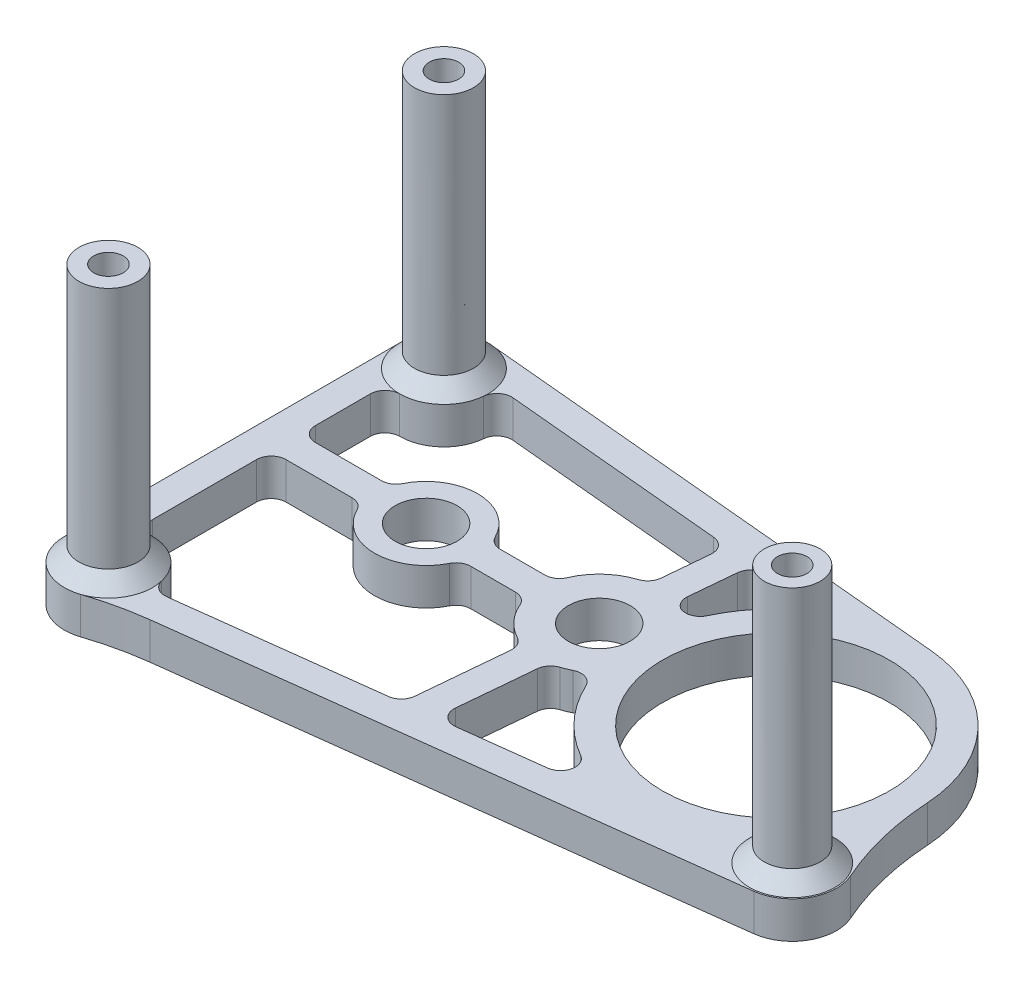
SolidWorks part; units mm, degrees
material "ABS"
ref_plane "Front Plane" through (0, 0, 0) normal (0, 0, 1) x (1, 0, 0)
ref_plane "Top Plane" through (0, 0, 0) normal (0, 1, 0) x (1, 0, 0)
ref_plane "Right Plane" through (0, 0, 0) normal (1, 0, 0) x (0, 0, -1)
sketch "Sketch2" plane through (0, 0, 0) normal (0, 1, 0) x (1, 0, 0)
  line L0 (-4.4632, 0) -> (-19.7032, 0)
  line L1 (-65.8645, -28.6002) -> (31.8874, -28.6002)
  line L2 (-65.8645, -28.6002) -> (-65.8645, 29.6837)
  line L3 (-65.8645, 29.6837) -> (31.8874, 29.6837)
  line L4 (31.8874, -28.6002) -> (31.8874, 29.6837)
  circle A0 centre (-4.4632, 0) radius 3.175 construction
  circle A1 centre (-19.7032, 0) radius 12.065 construction
  circle A2 centre (-4.4632, 0) radius 9.779
  circle A3 centre (-19.7032, 0) radius 2.667
  point P0 (0, 0)
  dimension "D1" = 6.35
  dimension "D2" = 24.13
  dimension "D3" = 19.558
  dimension "D5" = 5.334
  dimension "D4" = 15.24
extrude "Boss-Extrude1" add sketch "Sketch2" along normal blind 3.175
sketch "Sketch3" plane through (0, 3.175, 0) normal (0, 1, 0) x (1, 0, 0)
  line L4 (-65.8645, -28.6002) -> (31.8874, -28.6002)
  line L5 (31.8874, -28.6002) -> (31.8874, 29.6837)
  line L6 (31.8874, 29.6837) -> (-65.8645, 29.6837)
  line L7 (-65.8645, 29.6837) -> (-65.8645, -28.6002)
  line L8 (-65.8645, -28.6002) -> (31.8874, -28.6002)
  line L9 (31.8874, -28.6002) -> (31.8874, 29.6837)
  line L10 (31.8874, 29.6837) -> (-65.8645, 29.6837)
  line L11 (-65.8645, 29.6837) -> (-65.8645, -28.6002)
  dimension "D1" = 0
sketch "Sketch4" plane through (0, 3.175, 0) normal (0, 1, 0) x (1, 0, 0)
  line L0 (31.8874, -28.6002) -> (31.8874, 29.6837) construction
  line L1 (-65.8645, -28.6002) -> (31.8874, -28.6002) construction
  circle A0 centre (6.4874, -9.5502) radius 2.413
  circle A1 centre (6.4874, -9.5502) radius 1.27
  circle A2 centre (-45.4353, 12.3467) radius 1.27 construction
  circle A3 centre (-45.4353, 12.3467) radius 1.27
  circle A4 centre (-45.4353, -16.5723) radius 1.27 construction
  circle A5 centre (-45.4353, -16.5723) radius 1.27
  circle A6 centre (-45.4353, -16.5723) radius 2.54 construction
  circle A7 centre (-45.4353, -16.5723) radius 2.54
  circle A8 centre (-45.4353, 12.3467) radius 2.54 construction
  circle A9 centre (-45.4353, 12.3467) radius 2.54
  dimension "D1" = 2.54
  dimension "D2" = 4.826
  dimension "D3" = 25.4
  dimension "D4" = 19.05
extrude "Cut-Extrude1" cut sketch "Sketch4" against normal blind 38.354 contours A1 | A5 | A3
sketch "Sketch5" plane through (0, 3.175, 0) normal (0, 1, 0) x (1, 0, 0)
  circle A1 centre (-45.4353, -16.5723) radius 2.54
  circle A2 centre (-45.4353, -16.5723) radius 2.54
  circle A3 centre (-45.4353, -16.5723) radius 1.27
  circle A4 centre (-45.4353, -16.5723) radius 1.27
  circle A5 centre (-45.4353, 12.3467) radius 1.27
  circle A6 centre (-45.4353, 12.3467) radius 1.27
  circle A7 centre (6.4874, -9.5502) radius 1.27
  circle A8 centre (6.4874, -9.5502) radius 1.27
  circle A9 centre (6.4874, -9.5502) radius 2.413
  circle A10 centre (6.4874, -9.5502) radius 2.413
  circle A11 centre (-45.4353, 12.3467) radius 2.54
  circle A12 centre (-45.4353, 12.3467) radius 2.54
  dimension "D1" = 0
  dimension "D2" = 0
  dimension "D3" = 0
  dimension "D4" = 0
  dimension "D5" = 0
  dimension "D6" = 0
extrude "Boss-Extrude2" add sketch "Sketch5" along normal up to surface (22.225 mm away)
sketch "Sketch6" plane through (0, 0, 0) normal (0, -1, 0) x (1, 0, 0)
  line L0 (-3.3299, -12.2668) -> (-45.4353, -16.1567)
  line L1 (-49.2453, -12.3467) -> (-49.2453, 16.5723)
  line L2 (-47.0175, 20.0382) -> (6.9573, 13.3311)
  line L3 (-19.7032, 0) -> (-49.2453, 0)
  line L4 (-49.2453, 0) -> (-4.4632, 0)
  line L5 (-4.4632, 0) -> (-19.7032, 0)
  line L6 (-19.7032, 0) -> (-18.441, -13.6628)
  line L7 (-18.441, -13.6628) -> (-21.0196, 14.2481)
  line L8 (-47.3307, 17.5176) -> (6.644, 10.8105)
  line L9 (-46.7053, -12.3467) -> (-46.7053, 16.5723)
  line L10 (-3.5636, -9.7375) -> (-45.6689, -13.6275)
  line L11 (-19.7032, 1.27) -> (-49.2453, 1.27)
  line L12 (-19.7032, -1.27) -> (-49.2453, -1.27)
  line L13 (-20.9678, -0.1168) -> (-19.7056, -13.7796)
  line L14 (-18.4386, 0.1168) -> (-17.1764, -13.546)
  line L15 (-17.1764, -13.546) -> (-19.7549, 14.3649)
  line L16 (-19.7056, -13.7796) -> (-22.3098, 14.4084)
  line L17 (-19.7056, -13.7796) -> (-22.2842, 14.1313) construction
  circle A5 centre (-4.4632, 0) radius 12.319
  circle A6 centre (-4.4632, 0) radius 12.319
  circle A8 centre (6.4874, 9.5502) radius 3.81
  circle A9 centre (6.4874, 9.5502) radius 3.81
  circle A11 centre (-19.7032, 0) radius 5.207
  circle A12 centre (-19.7032, 0) radius 5.207
  circle A14 centre (-45.4353, -12.3467) radius 3.81
  circle A15 centre (-45.4353, -12.3467) radius 3.81
  circle A17 centre (-45.4353, 16.5723) radius 3.81
  circle A18 centre (-45.4353, 16.5723) radius 3.81
  dimension "D1" = 2.54
  dimension "D2" = 2.54
  dimension "D3" = 2.54
  dimension "D4" = 2.54
  dimension "D5" = 2.54
  dimension "D6" = 2.54
  dimension "D7" = 1.27
  dimension "D8" = 1.27
  dimension "D9" = 1.27
  dimension "D10" = 1.27
  dimension "D11" = 1.27
  dimension "D12" = 1.27
extrude "Cut-Extrude2" cut sketch "Sketch6" against normal blind 25.4
fillet "Fillet4" radius 25.4 1 edges at (6.4365, 1.5875, 5.7406)
chamfer "Chamfer1" distance 1.27 angle 45 3 edges at (6.4874, 3.175, 11.9632) (-45.4353, 3.175, 19.1123) (-45.4353, 3.175, -9.8067)
fillet "Fillet5" radius 1.27 20 edges at (-19.7293, 1.5875, 14.0878) (-5.2782, 1.5875, 12.292) (-16.1726, 1.5875, -3.8272) (-16.1726, 1.5875, 3.8272) (-17.9741, 1.5875, -4.9115) (-18.9032, 1.5875, 5.1452) (-17.41, 1.5875, -11.0168) (-11.0238, 1.5875, -10.4267) (-41.7374, 1.5875, -13.2643) (-20.5033, 1.5875, -5.1452) (-21.4324, 1.5875, 4.9115) (-24.753, 1.5875, -1.27) (-46.7053, 1.5875, -1.27) (-46.7053, 1.5875, -8.7546) (-19.9392, 1.5875, -11.2504) (-46.7053, 1.5875, 12.9802) (-46.7053, 1.5875, 1.27) (-22.3098, 1.5875, 14.4084) (-41.6327, 1.5875, 16.8096) (-24.753, 1.5875, 1.27)
fillet "Fillet6" radius 25.4 1 edges at (-43.0529, 1.5875, 19.5456)
sketch "Sketch10" plane through (0, 0, 0) normal (0, -1, 0) x (1, 0, 0)
  line L0 (-34.6257, 0) -> (-19.7032, 0)
  circle A0 centre (-19.7032, 0) radius 2.667 construction
  circle A1 centre (-19.7032, 0) radius 2.667
  circle A2 centre (-34.6257, 0) radius 4.445
  circle A3 centre (-34.6257, 0) radius 2.667
  dimension "D2" = 5.334
  dimension "D3" = 8.89
  dimension "D1" = 14.9225
extrude "Boss-Extrude4" add sketch "Sketch10" against normal blind 3.175
sketch "Sketch11" plane through (0, 0, 0) normal (0, -1, 0) x (1, 0, 0)
  arc A0 (-32.2805, 1.27) -> (-36.9709, 1.27) centre (-34.6257, 0) ccw construction
  arc A1 (-32.2805, 1.27) -> (-36.9709, 1.27) centre (-34.6257, 0) ccw
  circle A2 centre (-34.6257, 0) radius 2.667
extrude "Cut-Extrude4" cut sketch "Sketch11" against normal blind 11.049 contours A1 A2
fillet "Fillet8" radius 1.27 4 edges at (-38.8854, 1.5875, 1.27) (-30.366, 1.5875, 1.27) (-30.366, 1.5875, -1.27) (-38.8854, 1.5875, -1.27)
